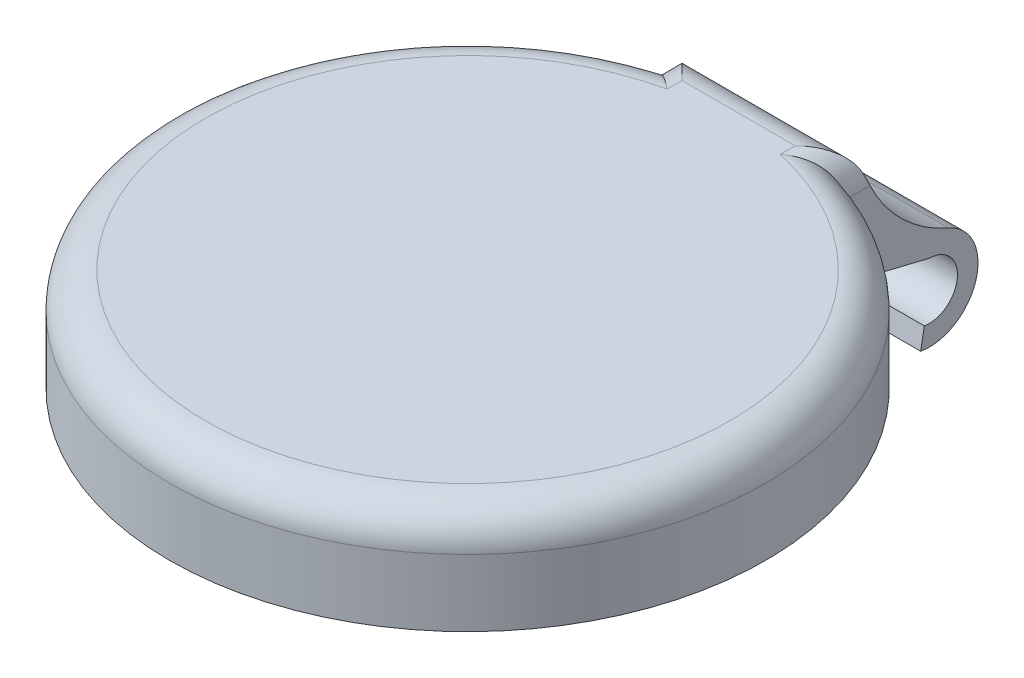
SolidWorks part; units mm, degrees
ref_plane "Front Plane" through (0, 0, 0) normal (0, 0, 1) x (1, 0, 0)
ref_plane "Top Plane" through (0, 0, 0) normal (0, 1, 0) x (1, 0, 0)
ref_plane "Right Plane" through (0, 0, 0) normal (1, 0, 0) x (0, 0, -1)
sketch "Sketch1" plane through (0, 0, 0) normal (0, 1, 0) x (1, 0, 0)
  line L0 (-9, 27.5681) -> (-9, 29)
  line L1 (-9, 29) -> (9, 29)
  line L2 (0, 0) -> (0, 37.5763) construction
  line L3 (9, 27.5681) -> (9, 29)
  arc A0 (-9, 27.5681) -> (9, 27.5681) centre (0, 0) ccw
  point P9 (0, 29)
  dimension "D1" = 58
  dimension "D2" = 9
extrude "Boss-Extrude1" add sketch "Sketch1" along normal blind 10
sketch "Sketch2" plane through (9, 0, 0) normal (1, 0, 0) x (0, 0, -1)
  line L0 (35.4225, -7.9582) -> (35.0752, -9.9278)
  line L5 (29, 10) -> (29, 0) construction
  line L6 (27.5681, 0) -> (29, 0)
  line L7 (29, 0) -> (29, 10)
  line L8 (29, 10) -> (27.5681, 10)
  line L9 (27.5681, 10) -> (27.5681, 0)
  line L12 (29, 10) -> (27.5681, 10)
  line L13 (27.5681, 10) -> (27.5681, 0)
  line L14 (29, -0.5) -> (29, 0)
  line L15 (29, 10) -> (29, 0)
  line L16 (27.5681, 0) -> (29, 0)
  line L17 (29, -0.5) -> (35.9, -0.5)
  line L18 (35.9, -2.5) -> (25.5681, 0)
  line L19 (-29, 0) -> (27.5681, 0) construction
  line L20 (25.5681, 0) -> (27.5681, 0)
  arc A0 (35.9, -2.5) -> (35.4225, -7.9582) centre (35.9, -5.25) cw
  arc A1 (35.9, -0.5) -> (35.0752, -9.9278) centre (35.9, -5.25) cw
  dimension "D1" = 170
  dimension "D4" = 2.75
  dimension "D2" = 6.9
  dimension "D7" = 2
  dimension "D5" = 0.5
  dimension "D3" = 2
  dimension "D6" = 0
extrude "Boss-Extrude2" add sketch "Sketch2" against normal blind 18 contours A1 A0 L0 region at (9, -5.5054, -38.8198)
fillet "Fillet3" radius 15 1 edges at (0, -0.5, -29)
fillet "Fillet4" radius 3.5 4 edges at (-9, 10, -28.284) (9, 10, -28.284) (0, 10, 29) (0, 10, -29)
sketch "Sketch13" plane through (0, 0, 0) normal (0, -1, 0) x (1, 0, 0)
  circle A0 centre (0, 0) radius 24
  arc A1 (9, -27.5681) -> (-9, -27.5681) centre (0, 0) ccw construction
  dimension "D1" = 5
extrude "Cut-Extrude1" cut sketch "Sketch13" against normal offset from surface (5 mm away) 5 up to face at (0, 10, -13.0284)
fillet "Fillet6" radius 15 1 edges at (0, 5, 24)
